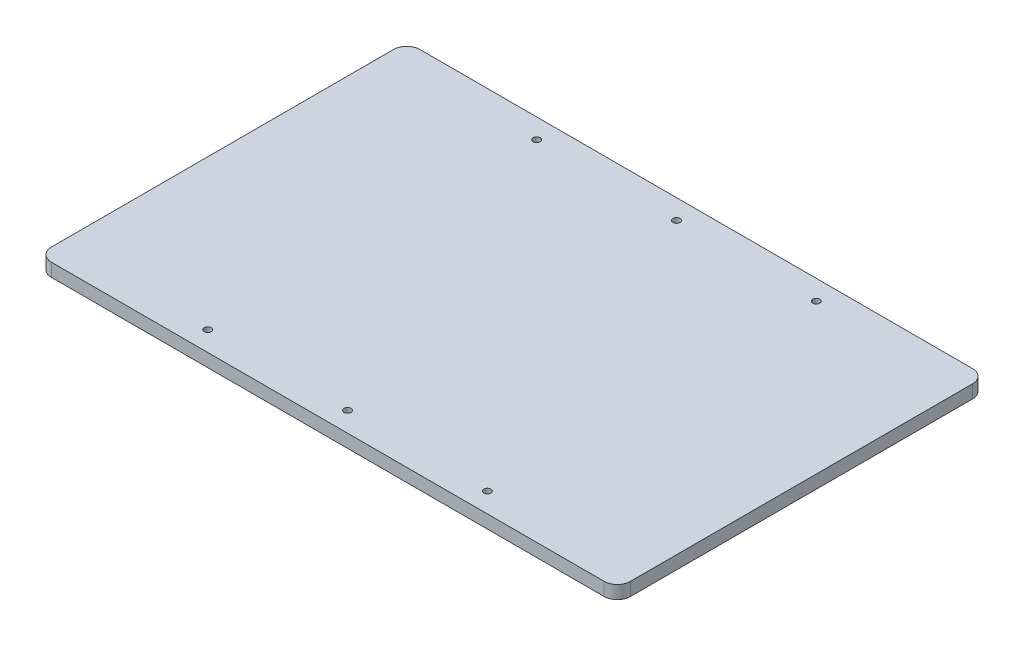
SolidWorks part; units mm, degrees
material "Acrylic (Medium-high impact)"
ref_plane "Front Plane" through (0, 0, 0) normal (0, 0, 1) x (1, 0, 0)
ref_plane "Top Plane" through (0, 0, 0) normal (0, 1, 0) x (1, 0, 0)
ref_plane "Right Plane" through (0, 0, 0) normal (1, 0, 0) x (0, 0, -1)
sketch "Sketch1" plane through (0, 0, 0) normal (0, 1, 0) x (1, 0, 0)
  line L0 (0, 0) -> (0, 88.9) construction
  line L1 (139.7, 88.9) -> (-139.7, 88.9) construction
  line L2 (139.7, 88.9) -> (139.7, -88.9) construction
  line L3 (139.7, -88.9) -> (-139.7, -88.9) construction
  line L4 (-139.7, 88.9) -> (-139.7, -88.9) construction
  line L5 (0, 0) -> (139.7, 0) construction
  line L6 (-139.7, 82.55) -> (-139.7, 44.45) construction
  line L7 (-139.7, 44.45) -> (-130.175, 44.45) construction
  line L8 (-130.175, 44.45) -> (-130.175, 63.5) construction
  line L9 (-123.825, 69.85) -> (-78.5812, 69.85) construction
  line L10 (-72.2312, 63.5) -> (-72.2313, 44.45) construction
  line L11 (-72.2313, 44.45) -> (-62.7062, 44.45) construction
  line L12 (-62.7062, 44.45) -> (-62.7062, 63.5) construction
  line L13 (-56.3562, 69.85) -> (-11.1125, 69.85) construction
  line L14 (-4.7625, 63.5) -> (-4.7625, 44.45) construction
  line L15 (-4.7625, 44.45) -> (4.7625, 44.45) construction
  line L16 (4.7625, 44.45) -> (4.7625, 63.5) construction
  line L17 (11.1125, 69.85) -> (56.3562, 69.85) construction
  line L18 (130.175, 63.5) -> (130.175, 44.45) construction
  line L19 (130.175, 44.45) -> (139.7, 44.45) construction
  line L20 (139.7, 44.45) -> (139.7, 82.55) construction
  line L21 (133.35, 88.9) -> (-133.35, 88.9) construction
  line L22 (62.7062, 63.5) -> (62.7062, 44.45) construction
  line L23 (62.7062, 44.45) -> (72.2313, 44.45) construction
  line L24 (72.2313, 44.45) -> (72.2313, 63.5) construction
  line L25 (78.5813, 69.85) -> (123.825, 69.85) construction
  line L26 (0, 44.45) -> (0, 69.85) construction
  line L27 (-133.35, 82.55) -> (-133.35, 88.9) construction
  line L28 (0, 0) -> (-82.1531, 0) construction
  line L29 (-120.2531, 63.5) -> (-82.1531, 63.5) construction
  line L30 (-120.2531, 63.5) -> (-120.2531, -63.5) construction
  line L31 (-120.2531, -63.5) -> (-82.1531, -63.5) construction
  line L32 (-82.1531, 63.5) -> (-82.1531, -63.5) construction
  line L33 (-101.2031, 63.5) -> (-101.2031, 69.85) construction
  line L34 (-120.2531, 63.5) -> (-130.175, 63.5) construction
  line L35 (139.7, 79.375) -> (-139.7, 79.375) construction
  line L36 (-33.7344, 69.85) -> (-33.7344, 79.375) construction
  line L37 (-33.7344, 79.375) -> (-33.7344, 88.9) construction
  line L38 (-67.4688, 44.45) -> (-67.4688, 79.375) construction
  line L39 (0, 44.45) -> (0, 79.375) construction
  line L40 (67.4688, 44.45) -> (67.4688, 79.375) construction
  line L42 (-133.35, 88.9) -> (133.35, 88.9)
  line L43 (-139.7, 82.55) -> (-139.7, -82.55)
  line L44 (-133.35, -88.9) -> (133.35, -88.9)
  line L45 (139.7, 82.55) -> (139.7, -82.55)
  arc A0 (123.825, 69.85) -> (130.175, 63.5) centre (123.825, 63.5) cw construction
  arc A1 (133.35, 88.9) -> (139.7, 82.55) centre (133.35, 82.55) cw construction
  arc A2 (-133.35, 88.9) -> (-139.7, 82.55) centre (-133.35, 82.55) ccw construction
  arc A3 (78.5813, 69.85) -> (72.2313, 63.5) centre (78.5813, 63.5) ccw construction
  arc A4 (56.3562, 69.85) -> (62.7062, 63.5) centre (56.3562, 63.5) cw construction
  arc A5 (11.1125, 69.85) -> (4.7625, 63.5) centre (11.1125, 63.5) ccw construction
  arc A6 (-11.1125, 69.85) -> (-4.7625, 63.5) centre (-11.1125, 63.5) cw construction
  arc A7 (-56.3562, 69.85) -> (-62.7062, 63.5) centre (-56.3562, 63.5) ccw construction
  arc A8 (-78.5812, 69.85) -> (-72.2312, 63.5) centre (-78.5812, 63.5) cw construction
  arc A9 (-123.825, 69.85) -> (-130.175, 63.5) centre (-123.825, 63.5) ccw construction
  circle A10 centre (-67.4688, 79.375) radius 1.7
  circle A11 centre (0, 79.375) radius 1.7
  circle A12 centre (67.4688, 79.375) radius 1.7
  circle A13 centre (67.4688, -79.375) radius 1.7
  circle A14 centre (0, -79.375) radius 1.7
  circle A15 centre (-67.4687, -79.375) radius 1.7
  arc A16 (-139.7, -82.55) -> (-133.35, -88.9) centre (-133.35, -82.55) ccw
  arc A17 (139.7, -82.55) -> (133.35, -88.9) centre (133.35, -82.55) cw
  arc A18 (139.7, 82.55) -> (133.35, 88.9) centre (133.35, 82.55) ccw
  arc A19 (-133.35, 88.9) -> (-139.7, 82.55) centre (-133.35, 82.55) ccw
  point P0 (0, 0)
  point P58 (-72.2312, 69.85)
  point P61 (-130.175, 69.85)
  point P80 (-270.4742, 78.2051)
  dimension "D8" = 6.35
  dimension "D10" = 3.4
  dimension "D3" = 6.35
  dimension "D1" = 6.35
  dimension "D2" = 279.4
  dimension "D4" = 45.2437
  dimension "D5" = 19.05
  dimension "D6" = 38.1
  dimension "D7" = 127
  dimension "D9" = 44.45
  dimension "D11" = 19.05
extrude "Boss-Extrude1" add sketch "Sketch1" along normal blind 6.35
equation "\"D11@Sketch1\"=\"D5@Sketch1\""
